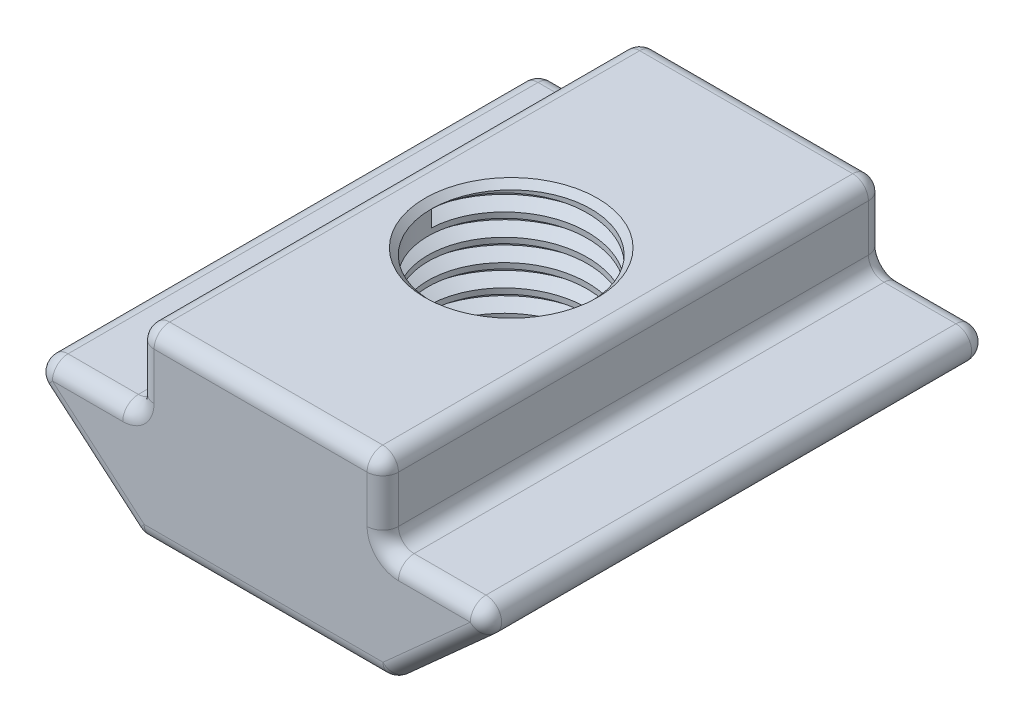
SolidWorks part; units mm, degrees
ref_plane "Ön Düzlem" through (0, 0, 0) normal (0, 0, 1) x (1, 0, 0)
ref_plane "Üst Düzlem" through (0, 0, 0) normal (0, 1, 0) x (1, 0, 0)
ref_plane "Sağ Düzlem" through (0, 0, 0) normal (1, 0, 0) x (0, 0, -1)
sketch "Çizim1" plane through (0, 0, 0) normal (0, 0, 1) x (1, 0, 0)
  line L0 (0, 0) -> (-7.8, 0)
  line L1 (-7.8, 0) -> (-7.8, -2.5)
  line L2 (-7.8, -2.5) -> (-11.9, -2.5)
  line L3 (-11.9, -2.5) -> (-7.8, -6)
  line L4 (-7.8, -6) -> (0.2, -6)
  line L5 (0, 0) -> (0, -2.5)
  line L6 (0, -2.5) -> (4.1, -2.5)
  line L7 (4.1, -2.5) -> (0.2, -6)
  dimension "D2" = 6
  dimension "D1" = 7.8
  dimension "D3" = 16
  dimension "D4" = 2.5
extrude "Yükseklik-Ekstrüzyon1" add sketch "Çizim1" along normal mid plane 16
sketch "Çizim2" plane through (0, 0, 0) normal (0, 1, 0) x (1, 0, 0)
  circle A0 centre (-3.9, 0) radius 2.55
  dimension "D1" = 5.1
extrude "Kes-Ekstrüzyon3" cut sketch "Çizim2" against normal through all contours A0
chamfer "Pah2" distance 0.2 angle 45 1 edges at (-6.45, 0, 0)
thread "Diş1" pitch 0.7 method cut profile "Diş Profili1" start angle 0, offset 0, length 6, pitch 0.7, diameter 5.1
ref_plane "Düzlem1" through (-6.45, -0.2, 0) normal (0, 0, 1) x (-1, 0, 0)
sketch "Diş Profili1" plane through (-6.45, -0.2, 0) normal (0, 0, 1) x (-1, 0, 0)
  line L0 (0, 0) -> (0, 0.7) construction
  line L1 (0, 0) -> (0.3789, 0.2187)
  line L2 (0.3789, 0.2187) -> (0.3789, 0.3062)
  line L3 (0.3789, 0.3062) -> (0, 0.525)
  line L4 (0.3789, 0.2625) -> (0, 0.2625) construction
  line L11 (0, 0) -> (0, 0.525)
  point P2 (0, 0)
  dimension "Pitch" = 0.7
  dimension "Profile_Angle" = 60
  dimension "Profile_Land" = 0.0875
  dimension "Profile_Height" = 0.3789
fillet "Radyus1" radius 0.5 24 edges at (-9.85, -2.5, -8) (0.2, -6, 0) (4.1, -2.5, 0) (0, 0, 0) (0, -2.5, 0) (-3.8, -6, -8) (2.15, -4.25, -8) (2.05, -2.5, -8) (0, -1.25, -8) (-3.9, 0, -8) (-9.85, -4.25, -8) (-7.8, -6, 0) (-3.9, 0, 8) (0, -1.25, 8) (2.05, -2.5, 8) (2.15, -4.25, 8) (-3.8, -6, 8) (-9.85, -4.25, 8) (-9.85, -2.5, 8) (-7.8, -1.25, 8) (-7.8, -1.25, -8) (-7.8, 0, 0) (-7.8, -2.5, 0) (-11.9, -2.5, 0)
